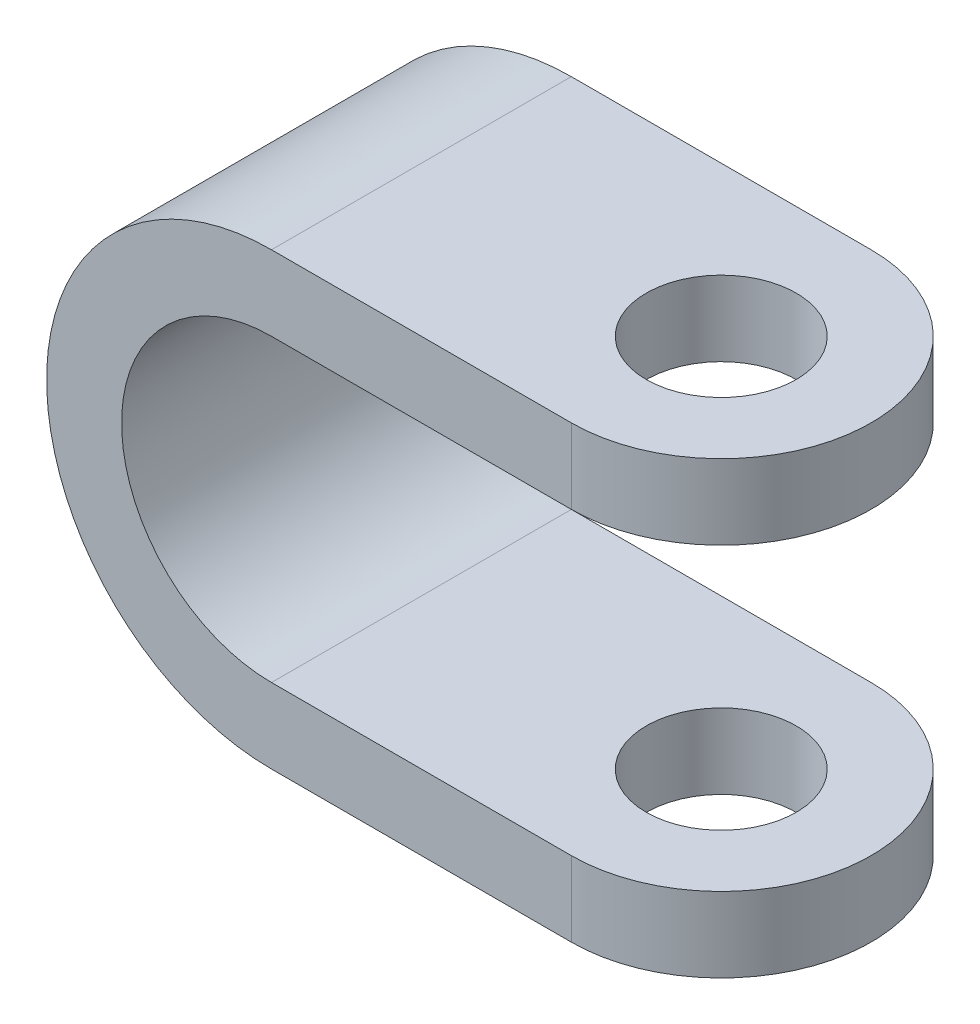
SolidWorks part; units mm, degrees
ref_plane "Front Plane" through (0, 0, 0) normal (0, 0, 1) x (1, 0, 0)
ref_plane "Top Plane" through (0, 0, 0) normal (0, 1, 0) x (1, 0, 0)
ref_plane "Right Plane" through (0, 0, 0) normal (1, 0, 0) x (0, 0, -1)
sketch "Sketch1" plane through (0, 0, 0) normal (0, 0, 1) x (1, 0, 0)
  line L0 (0, -15) -> (-60, -15)
  line L1 (-60, -55) -> (0, -55)
  arc A0 (-60, -15) -> (-60, -55) centre (-60, -35) ccw
  dimension "D3" = 20
  dimension "D1" = 15
  dimension "D2" = 60
extrude "Extrude-Thin1" add sketch "Sketch1" along normal blind 90 thin contours L0 A0 L1 thin type one direction wall 10
sketch "Sketch2" plane through (0, 0, 0) normal (0, 1, 0) x (1, 0, 0)
  line L0 (-90, -25) -> (-90, -65)
  line L1 (-90, -25) -> (-20, -25)
  line L2 (-90, -65) -> (-20, -65)
  line L3 (0, -90) -> (0, 0) construction
  line L4 (-90, 0) -> (-90, -90) construction
  arc A0 (-20, -25) -> (-20, -65) centre (-20, -45) cw
  circle A1 centre (-20, -45) radius 10
  dimension "D2" = 20
  dimension "D5" = 20
  dimension "D1" = 40
  dimension "D3" = 25
extrude "Boss-Extrude1" add sketch "Sketch2" against normal blind 90 separate body
combine bodies "Combine1" operation type common bodies to combine 102 101
